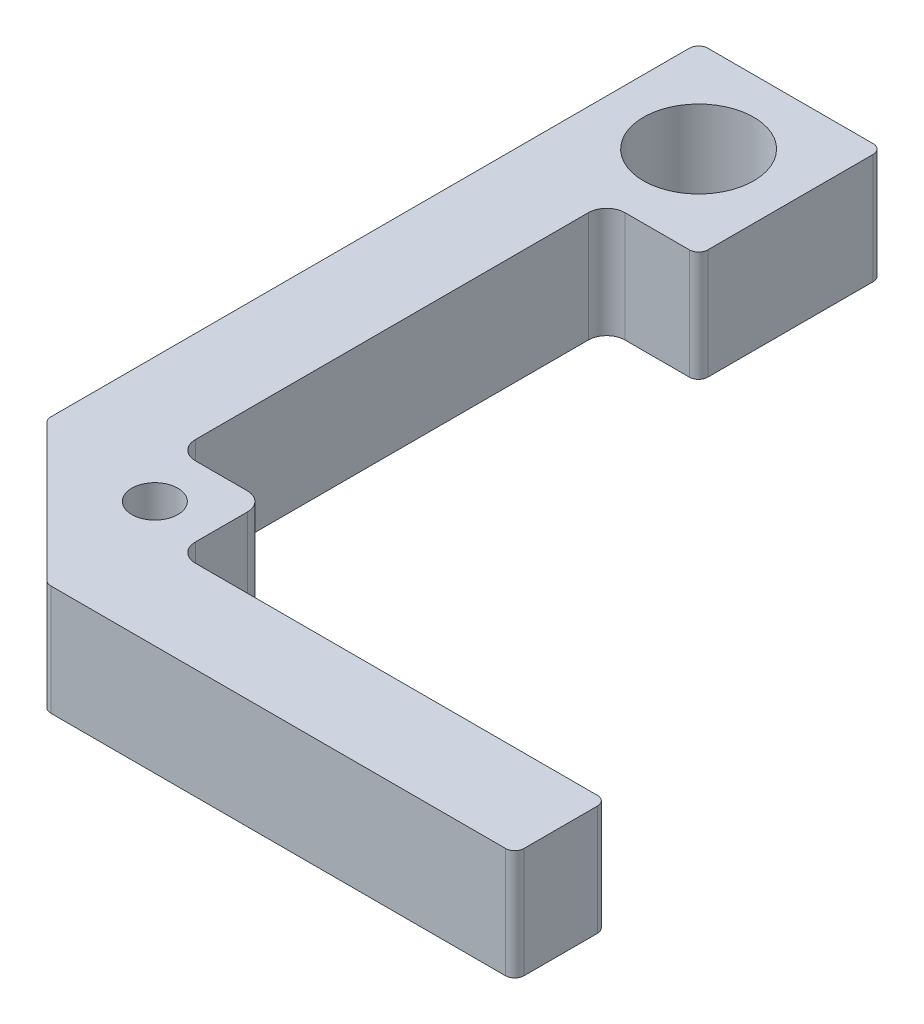
SolidWorks part; units mm, degrees
ref_plane "Front Plane" through (0, 0, 0) normal (0, 0, 1) x (1, 0, 0)
ref_plane "Top Plane" through (0, 0, 0) normal (0, 1, 0) x (1, 0, 0)
ref_plane "Right Plane" through (0, 0, 0) normal (1, 0, 0) x (0, 0, -1)
sketch "Sketch1" plane through (0, 0, 0) normal (0, 1, 0) x (1, 0, 0)
  line L0 (-66.4, 15.5079) -> (-50.8921, 0)
  line L1 (0, 0) -> (-50.8921, 0)
  line L2 (0, 0) -> (0, 10)
  line L3 (0, 10) -> (-46.75, 10)
  line L4 (-56.4, 66.4) -> (-66.4, 66.4) construction
  line L5 (-56.4, 66.4) -> (-46.4, 66.4)
  line L6 (-56.4, 19.65) -> (-56.4, 66.4)
  line L7 (-56.4, 19.65) -> (-46.75, 10) construction
  line L8 (-66.4, 15.5079) -> (-66.4, 66.4)
  line L9 (-46.75, 10) -> (-46.75, 19.65)
  line L10 (-46.75, 19.65) -> (-56.4, 19.65)
  line L11 (-66.4, 66.4) -> (-66.4, 86.4)
  line L12 (-66.4, 86.4) -> (-46.4, 86.4)
  line L13 (-46.4, 66.4) -> (-46.4, 86.4)
  circle A0 centre (-56.4, 76.4) radius 6
  point P15 (-51.575, 14.825)
  point P16 (-58.6461, 7.7539)
  dimension "D7" = 12
  dimension "D1" = 56.4
  dimension "D2" = 10
  dimension "D3" = 10
  dimension "D4" = 46.75
  dimension "D5" = 56.4
  dimension "D6" = 135
  dimension "D8" = 20
  dimension "D9" = 20
  dimension "D10" = 10
  dimension "D11" = 10
  dimension "D12" = 10
extrude "Boss-Extrude1" add sketch "Sketch1" along normal blind 12
sketch "Sketch3" plane through (0, 0, 0) normal (0, -1, 0) x (1, 0, 0)
  line L1 (-46.75, -19.65) -> (-56.4, -19.65)
  line L2 (-46.75, -19.65) -> (-46.75, -10)
  line L3 (-46.75, -10) -> (-56.4, -10)
  line L4 (-56.4, -19.65) -> (-56.4, -10)
extrude "Cut-Extrude1" cut sketch "Sketch3" against normal blind 1
sketch "Sketch4" plane through (0, 1, 0) normal (0, -1, 0) x (1, 0, 0)
  line L0 (-55.2787, -13.6213) -> (-56.4, -13.6213) construction
  line L1 (-56.4, -10) -> (-56.4, -19.65) construction
  line L2 (-52.7787, -11.1213) -> (-52.7787, -10) construction
  line L3 (-46.75, -10) -> (-56.4, -10) construction
  circle A0 centre (-52.7787, -13.6213) radius 2.5
  dimension "D1" = 5
  dimension "D2" = 1.1213
extrude "Cut-Extrude2" cut sketch "Sketch4" against normal through all
fillet "Fillet - Outer Stepper" radius 2 2 edges at (-56.4, 0.5, -10) (-56.4, 6, -66.4)
fillet "Fillet - Inner Stepper" radius 2 1 edges at (-46.75, 6.5, -19.65)
fillet "Fillet - Outer Stepper2" radius 2 2 edges at (-46.75, 6.5, -10) (-56.4, 6.5, -19.65)
fillet "Fillet5" radius 1 7 edges at (-66.4, 6, -86.4) (-46.4, 6, -86.4) (-46.4, 6, -66.4) (-66.4, 6, -15.5079) (-50.8921, 6, 0) (0, 6, 0) (0, 6, -10)
